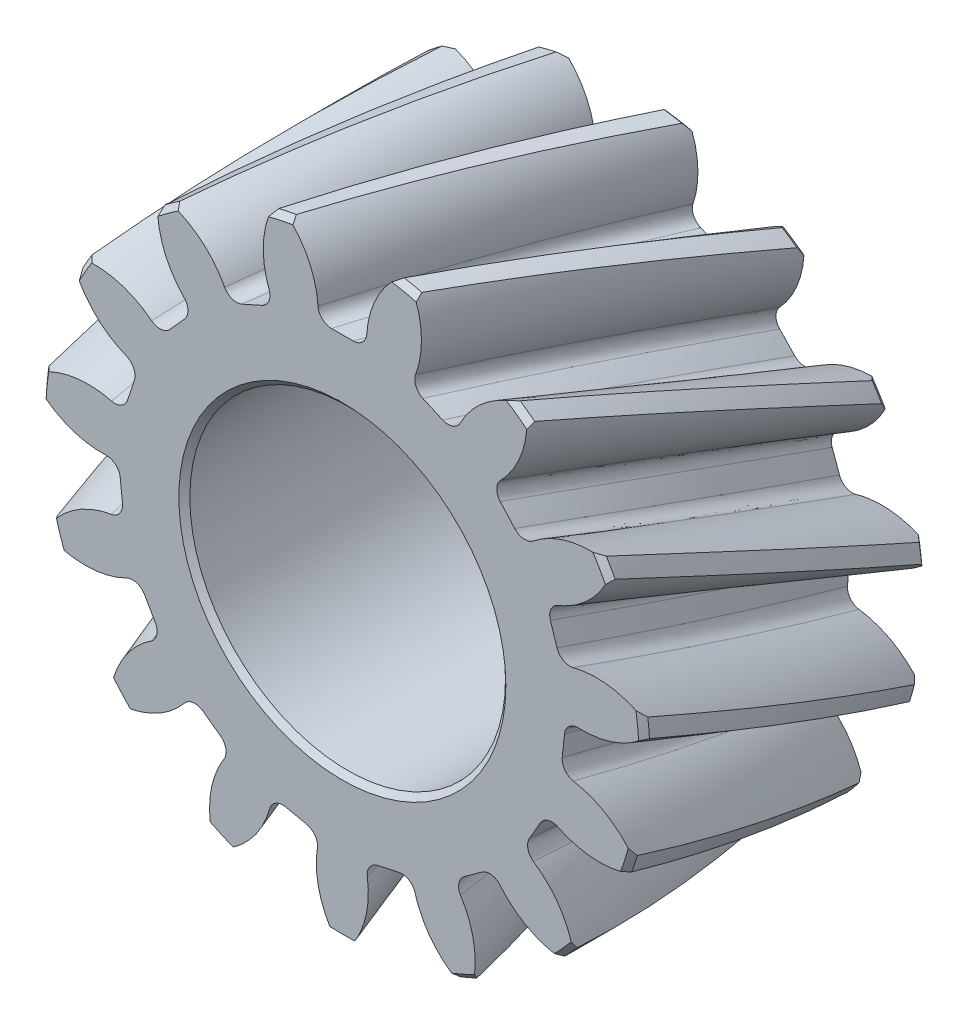
SolidWorks part; units mm, degrees
ref_plane "Front Plane" through (0, 0, 0) normal (0, 0, 1) x (1, 0, 0)
ref_plane "Top Plane" through (0, 0, 0) normal (0, 1, 0) x (1, 0, 0)
ref_plane "Right Plane" through (0, 0, 0) normal (1, 0, 0) x (0, 0, -1)
sketch "Sketch2" plane through (0, 0, 0) normal (0, 0, 1) x (1, 0, 0)
  circle A0 centre (0, 0) radius 10.625
  dimension "D1" = 21.25
extrude "Boss-Extrude1" add sketch "Sketch2" along normal blind 10
hole_wizard "M6 Tapped Hole1" positions "Sketch3" profile "Sketch4" tap size "M6" standard "ISO" end condition through all
sketch "Sketch3" plane through (0, 0, 10) normal (0, 0, 1) x (1, 0, 0)
  point P0 (0, 0)
sketch "Sketch4" plane through (0, 0, 10) normal (1, 0, 0) x (0, -1, 0)
  line L0 (0, 0) -> (0, 10)
  line L1 (0, 10) -> (5.55, 10)
  line L2 (5.55, 10) -> (5.55, 0)
  line L5 (5.55, 0) -> (0, 0)
  line L11 (0, -6.35) -> (0, 107.95) construction
  dimension "Thru Tap Drill Dia." = 11.1
  dimension "Thru Tap Drill Depth" = 10
chamfer "Chamfer2" distance 0.2 angle 43 4 edges at (10.625, 0, 0) (5.55, 0, 0) (10.625, 0, 10) (5.55, 0, 10) first distance on face at (5.55, 0, 0) first distance on face at (10.625, 0, 10) first distance on face at (5.55, 0, 10)
sketch "Sketch5" plane through (0, 0, 10) normal (0, 0, 1) x (1, 0, 0)
  circle A0 centre (0, 0) radius 10.625
  dimension "D1" = 21.25
curve "Helix/Spiral1" pitch 161.84 height 10 turns 0.0618
sketch "Sketch8" plane through (0, 0, 10) normal (0, 0, 1) x (1, 0, 0)
  line L0 (0, 0) -> (0, 10.625)
  line L1 (-0.38, 7.815) -> (0.38, 7.815)
  arc A0 (1.9, 10.4537) -> (-1.9, 10.4537) centre (0, 0) ccw
  circle A1 centre (0, 0) radius 10.625 construction
  arc A2 (-1.9, 10.4537) -> (-0.8582, 8.2537) centre (-4.1027, 8.064) cw
  arc A3 (-0.8582, 8.2537) -> (-0.38, 7.815) centre (-0.38, 8.295) ccw
  arc A4 (0.8582, 8.2537) -> (0.38, 7.815) centre (0.38, 8.295) cw
  arc A5 (1.9, 10.4537) -> (0.8582, 8.2537) centre (4.1027, 8.064) ccw
  point P14 (0, 7.815)
  dimension "D2" = 3.25
  dimension "D3" = 0.48
  dimension "D1" = 3.8
  dimension "D4" = 2.81
  dimension "D5" = 0.38
  dimension "D6" = 2.2
sweep "Cut-Sweep1" cut profiles "Sketch8" path "Helix/Spiral1" align with end faces yes
pattern_circular "CirPattern1" count 15 over 360 about axis through (0, 0, 10) along (0, 0, 1) of "Cut-Sweep1" reverse direction yes
